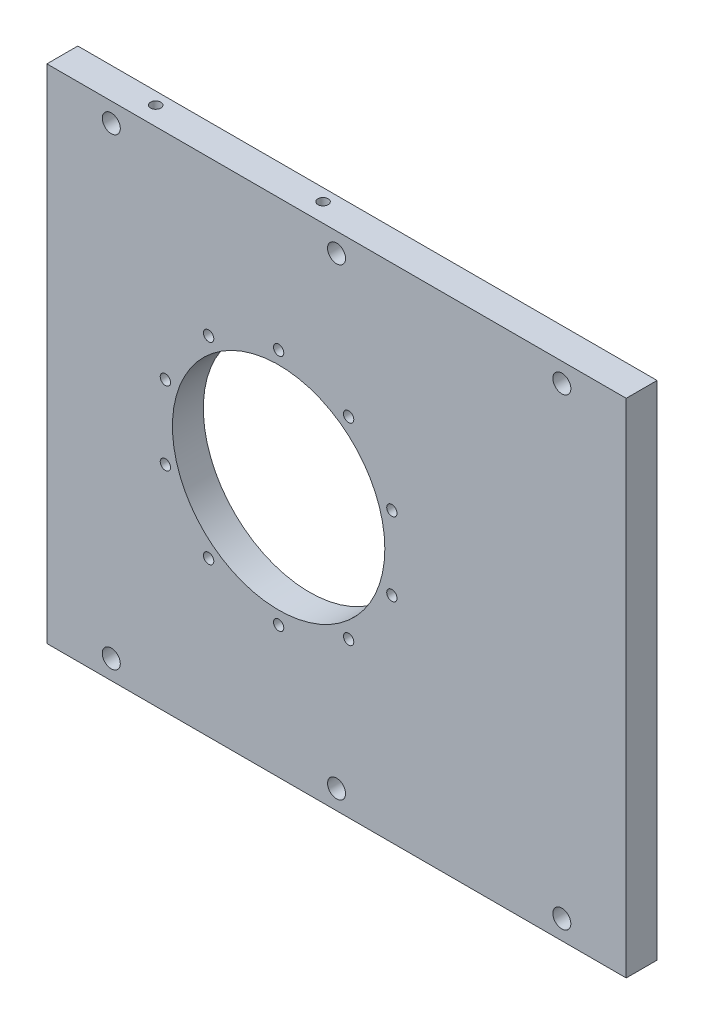
SolidWorks part; units mm, degrees
ref_plane "前视基准面" through (0, 0, 0) normal (0, 0, 1) x (1, 0, 0)
ref_plane "上视基准面" through (0, 0, 0) normal (0, 1, 0) x (1, 0, 0)
ref_plane "右视基准面" through (0, 0, 0) normal (1, 0, 0) x (0, 0, -1)
other "Configuration Table"
sketch "草图1" plane through (0, 0, 0) normal (0, 0, 1) x (1, 0, 0)
  line L0 (-225, 0) -> (225, 0) construction
  line L1 (-225, 195) -> (225, 195)
  line L2 (-225, 195) -> (-225, -195)
  line L3 (-225, -195) -> (225, -195)
  line L4 (225, 195) -> (225, -195)
  line L5 (-225, 195) -> (225, -195) construction
  line L6 (-225, -195) -> (225, 195) construction
  line L7 (0, 195) -> (0, -195) construction
  circle A0 centre (-45, 0) radius 82.5
  circle A1 centre (-45, 0) radius 92.5 construction
  circle A2 centre (-45, 92.5) radius 4
  circle A3 centre (9.3701, 74.8341) radius 4
  circle A4 centre (42.9727, 28.5841) radius 4
  circle A5 centre (42.9727, -28.5841) radius 4
  circle A6 centre (9.3701, -74.8341) radius 4
  circle A7 centre (-45, -92.5) radius 4
  circle A8 centre (-99.3701, -74.8341) radius 4
  circle A9 centre (-132.9727, -28.5841) radius 4
  circle A10 centre (-132.9727, 28.5841) radius 4
  circle A11 centre (-99.3701, 74.8341) radius 4
  circle A12 centre (0, 180) radius 7
  circle A13 centre (-175, 180) radius 7
  circle A14 centre (175, 180) radius 7
  circle A15 centre (-175, -180) radius 7
  circle A16 centre (0, -180) radius 7
  circle A17 centre (175, -180) radius 7
  point P0 (0, 0)
  point P33 (-45, 0)
  dimension "D4" = 165
  dimension "D5" = 185
  dimension "D6" = 8
  dimension "D8" = 14
  dimension "D1" = 450
  dimension "D2" = 390
  dimension "D3" = 180
  dimension "D9" = 350
  dimension "D10" = 360
  dimension "D7" = 10
extrude "凸台-拉伸1" add sketch "草图1" along normal blind 24 contours L4 L3 L2 L1 | A0
extrude "切除-拉伸1" cut sketch "草图1<3>" against normal blind 18 from surface contours A13 | A12 | A14 | A10 | A11 | A2 | A3 | A4 | A5 | A6 | A7 | A8 | A9 | A15 | A16 | A17 starting at face at (0, 0, 24)
sketch "草图1<3>" plane through (0, 0, 0) normal (0, 0, 1) x (1, 0, 0) same geometry as "草图1"
sketch "草图2" plane through (0, 195, 0) normal (0, -1, 0) x (1, 0, 0)
  line L0 (-225, 24) -> (-225, 0) construction
  line L1 (-225, 24) -> (225, 24) construction
  circle A0 centre (-155, 9.5) radius 4
  circle A1 centre (-25, 9.5) radius 4
  dimension "D2" = 8
  dimension "D3" = 70
  dimension "D1" = 130
  dimension "D4" = 14.5
extrude "切除-拉伸2" cut sketch "草图2" along normal blind 20
